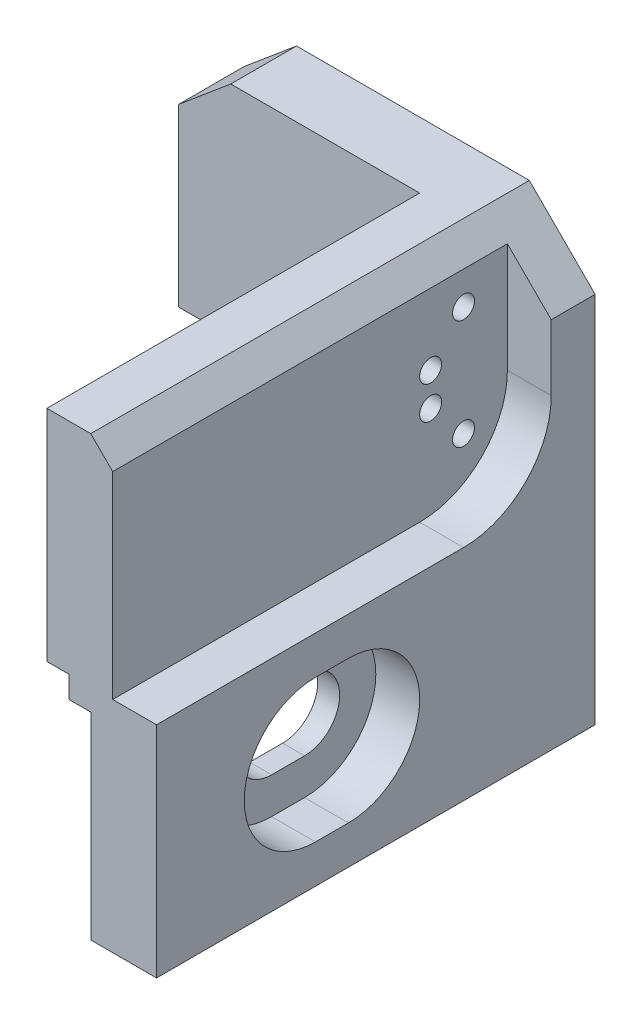
SolidWorks part; units mm, degrees
material "2024-T3"
ref_plane "Спереди" through (0, 0, 0) normal (0, 0, 1) x (1, 0, 0)
ref_plane "Сверху" through (0, 0, 0) normal (0, 1, 0) x (1, 0, 0)
ref_plane "Справа" through (0, 0, 0) normal (1, 0, 0) x (0, 0, -1)
sketch "Эскиз1" plane through (0, 0, 0) normal (0, 0, 1) x (1, 0, 0)
  line L0 (0, 0) -> (1, 0)
  line L1 (1, 0) -> (1, -9)
  line L2 (1, -9) -> (4, -9)
  line L3 (4, -9) -> (4, 11)
  line L4 (4, 11) -> (-12, 11)
  line L5 (-12, 11) -> (-12, 1)
  line L6 (-12, 1) -> (0, 1)
  line L7 (0, 1) -> (0, 0)
  dimension "D1" = 1
  dimension "D2" = 3
  dimension "D3" = 16
  dimension "D4" = 10
  dimension "D5" = 1
  dimension "D6" = 9
extrude "Бобышка-Вытянуть1" add sketch "Эскиз1" along normal blind 20
sketch "Эскиз2" plane through (-12, 0, 0) normal (-1, 0, 0) x (0, 0, 1)
  line L0 (3, 11) -> (3, 1)
  line L1 (20, 11) -> (0, 11) construction
  line L2 (20, 1) -> (0, 1) construction
  line L4 (0, 11) -> (0, 1) construction
  line M2 (0, 1) -> (20, 1)
  line M3 (20, 1) -> (20, 11)
  line M4 (20, 11) -> (0, 11)
  dimension "D1" = 3
extrude "Вырез-Вытянуть1" cut sketch "Эскиз2" against normal offset from surface (11 mm away) 2 contours L0 M4 M2 M3 region at (-12, 6, 11.5) up to face at (1, -4.5, 10)
sketch "Эскиз3" plane through (4, 0, 0) normal (1, 0, 0) x (0, 0, -1)
  line L0 (-12.75, -4) -> (-11.25, -4) construction
  line L1 (-12.75, -2.4) -> (-11.25, -2.4)
  line L2 (-12.75, -5.6) -> (-11.25, -5.6)
  line L3 (0, -9) -> (0, 11) construction
  line L4 (-20, 0) -> (0, 0) construction
  line L5 (-12.75, -0.75) -> (-11.25, -0.75)
  line L6 (-12.75, -7.25) -> (-11.25, -7.25)
  arc A0 (-12.75, -2.4) -> (-12.75, -5.6) centre (-12.75, -4) ccw
  arc A1 (-11.25, -5.6) -> (-11.25, -2.4) centre (-11.25, -4) ccw
  arc A2 (-11.25, -7.25) -> (-11.25, -0.75) centre (-11.25, -4) ccw
  arc A3 (-12.75, -0.75) -> (-12.75, -7.25) centre (-12.75, -4) ccw
  point P2 (-12, -4)
  dimension "D2" = 4
  dimension "D3" = 12
  dimension "D4" = 1.5
  dimension "D1" = 3.2
  dimension "D5" = 1.65
extrude "Вырез-Вытянуть2" cut sketch "Эскиз3" against normal up to next contours L2 A1 L1 A0 region at (4, -4, 12)
chamfer "Фаска1" distance 3 angle 45 1 edges at (4, 11, 10)
chamfer "Фаска2" distance 2 angle 50 1 edges at (-12, 11, 1.5) first distance on face at (-12, 6, 1.5)
extrude "Вырез-Вытянуть3" cut sketch "Эскиз3<3>" against normal blind 2
sketch "Эскиз3<3>" plane through (4, 0, 0) normal (1, 0, 0) x (0, 0, -1) same geometry as "Эскиз3"
sketch "Эскиз4" plane through (4, 0, 0) normal (1, 0, 0) x (0, 0, -1)
  line L0 (-3, 11) -> (-3, 1) construction
  line L1 (-20, -9) -> (-20, 8) construction
  line L2 (-20, 1) -> (-6, 1)
  line L3 (-20, 0) -> (0, 0) construction
  line L5 (-20, 10) -> (-20, 1)
  line L6 (-2, 5) -> (-2, 11)
  line L7 (-20, 11) -> (0, 11) construction
  line L8 (-2, 11) -> (-20, 11)
  line L9 (-20, 11) -> (-20, 10)
  arc A0 (-2, 5) -> (-6, 1) centre (-6, 5) cw
  line M6 (0, 8) -> (-20, 8)
  line M7 (-20, 8) -> (-20, -9)
  dimension "D3" = 4
  dimension "D1" = 1
  dimension "D2" = 1
extrude "Вырез-Вытянуть4" cut sketch "Эскиз4" against normal blind 2 contours A0 L5 M6 | A0 L2 M6 M7 region at (4, 4.573, 11.2271) region at (4, 9.5, 11)
sketch "Эскиз5" plane through (-1, 0, 0) normal (-1, 0, 0) x (0, 0, 1)
  line L0 (20, 0) -> (0, 0) construction
  line L1 (3, 9) -> (3, 1) construction
  line L2 (3, 11) -> (3, 1) construction
  circle A0 centre (4, 8.5) radius 0.5
  circle A1 centre (5.5, 6.75) radius 0.5
  circle A2 centre (5.5, 5.25) radius 0.5
  circle A3 centre (4, 3.5) radius 0.5
  dimension "D1" = 2.5
  dimension "D2" = 1.5
  dimension "D3" = 5
  dimension "D6" = 1
  dimension "D7" = 1.75
  dimension "D4" = 3.5
  dimension "D5" = 1
extrude "Вырез-Вытянуть5" cut sketch "Эскиз5" against normal through all
